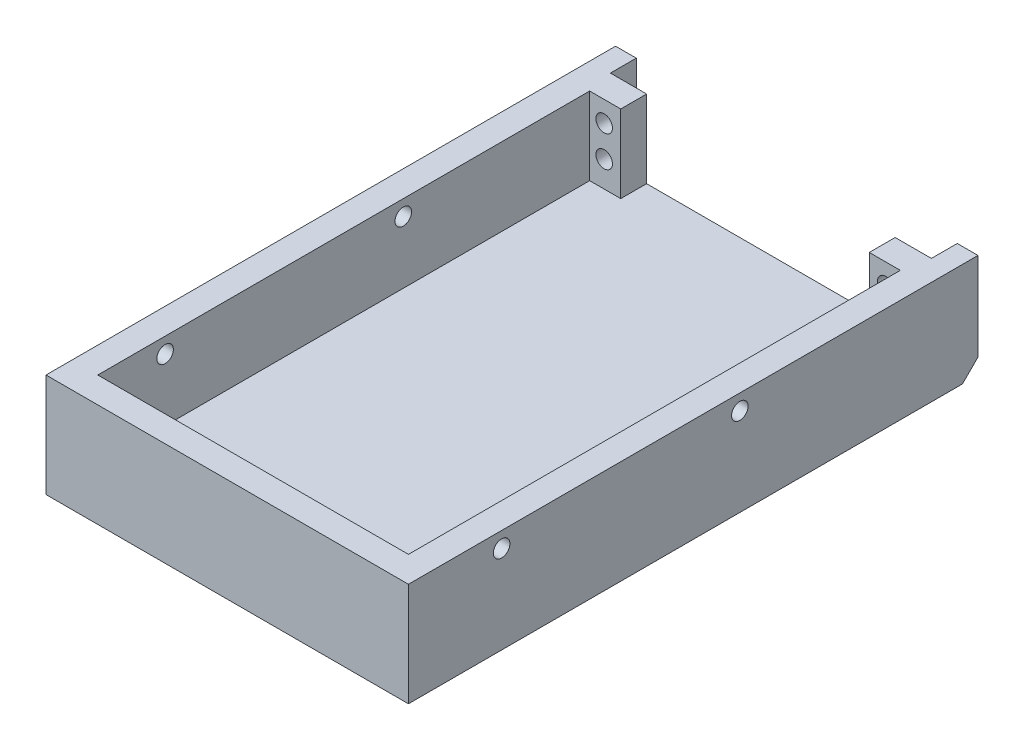
SolidWorks part; units mm, degrees
ref_plane "Alzado" through (0, 0, 0) normal (0, 0, 1) x (1, 0, 0)
ref_plane "Planta" through (0, 0, 0) normal (0, 1, 0) x (1, 0, 0)
ref_plane "Vista lateral" through (0, 0, 0) normal (1, 0, 0) x (0, 0, -1)
sketch "Croquis1" plane through (0, 0, 0) normal (0, 1, 0) x (1, 0, 0)
  line L1 (-35, -52.5) -> (35, -52.5)
  line L2 (-35, -52.5) -> (-35, 52.5)
  line L3 (-35, 52.5) -> (35, 52.5)
  line L4 (35, -52.5) -> (35, 52.5)
  line L5 (-35, -52.5) -> (35, 52.5) construction
  line L6 (-35, 52.5) -> (35, -52.5) construction
  point P0 (0, 0)
  dimension "D1" = 105
  dimension "D2" = 70
extrude "Saliente-Extruir1" add sketch "Croquis1" along normal blind 20
shell "Vaciado1" thickness 5 removed face at (0, 20, 0)
sketch "Croquis3" plane through (-35, 0, 0) normal (-1, 0, 0) x (0, 0, 1)
  line L0 (34.5, 17) -> (-11.5, 17) construction
  line L1 (52.5, 20) -> (52.5, 0) construction
  line L2 (-52.5, 20) -> (52.5, 20) construction
  circle A0 centre (34.5, 17) radius 1.6
  circle A1 centre (-11.5, 17) radius 1.6
  dimension "D1" = 3.2
  dimension "D2" = 3.2
  dimension "D3" = 46
  dimension "D4" = 18
  dimension "D5" = 3
extrude "Cortar-Extruir1" cut sketch "Croquis3" against normal blind 70
sketch "Croquis4" plane through (0, 0, -52.5) normal (0, 0, -1) x (-1, 0, 0)
  line L0 (-35, 20) -> (35, 20) construction
  line L1 (-30, 20) -> (30, 20)
  line L2 (-30, 20) -> (-30, 5)
  line L3 (-30, 5) -> (30, 5)
  line L4 (30, 20) -> (30, 5)
  line L5 (-35, 0) -> (35, 0) construction
  line L6 (35, 20) -> (35, 0) construction
  line L7 (-35, 20) -> (-35, 0) construction
  dimension "D1" = 5
  dimension "D2" = 5
  dimension "D3" = 5
extrude "Cortar-Extruir2" cut sketch "Croquis4" against normal blind 5
sketch "Croquis5" plane through (-30, 0, 0) normal (1, 0, 0) x (0, 0, -1)
  line L0 (-52.5, 20) -> (52.5, 20) construction
  line L1 (47.5, 20) -> (52.5, 20)
  line L2 (47.5, 20) -> (47.5, 5)
  line L3 (47.5, 5) -> (52.5, 5)
  line L4 (52.5, 20) -> (52.5, 5)
  dimension "D1" = 5
extrude "Saliente-Extruir2" add sketch "Croquis5" along normal blind 6
mirror "Simetría1" about plane through (0, 0, 0) normal (1, 0, 0) of "Saliente-Extruir2"
sketch "Croquis6" plane through (0, 0, -52.5) normal (0, 0, -1) x (-1, 0, 0)
  line L0 (-27.2, 16) -> (-27.2, 10) construction
  line L1 (-35, 20) -> (-24, 20) construction
  line L2 (-24, 5) -> (-24, 20) construction
  line L3 (-35, 20) -> (-35, 0) construction
  line L4 (-35, 0) -> (35, 0) construction
  circle A0 centre (-27.2, 16) radius 1.6
  circle A1 centre (-27.2, 10) radius 1.6
  dimension "D1" = 3.2
  dimension "D2" = 3.2
  dimension "D3" = 4
  dimension "D4" = 6
  dimension "D5" = 3.2
extrude "Cortar-Extruir3" cut sketch "Croquis6" against normal up to next
mirror "Simetría2" about plane through (0, 0, 0) normal (1, 0, 0) of "Cortar-Extruir3"
sketch "Croquis7" plane through (0, 0, 0) normal (0, 1, 0) x (1, 0, 0)
  line L0 (35, 57.5) -> (31, 57.5) construction
  line L1 (35, 57.5) -> (31, 57.5)
  line L2 (35, 57.5) -> (35, 52.5)
  line L3 (35, 52.5) -> (31, 52.5)
  line L4 (31, 57.5) -> (31, 52.5)
  point P6 (31.5357, 57.5)
  point P7 (31.7237, 57.5)
  point P8 (32.9266, 57.5)
  point P9 (31.0245, 57.5)
  point P10 (0, 0)
  point P11 (0, 0)
  point P12 (31, 52.2852)
  point P13 (31, 52.2852)
  point P14 (35, 52.5)
  point P16 (0, 0)
  point P17 (35, 57.5)
  point P18 (35, 57.624)
  point P19 (35, 57.4485)
  point P20 (35, 57.492)
  point P21 (31, 57.4093)
  point P22 (35, 56.2398)
  point P23 (35, 59.0477)
  point P24 (31, 57.5)
  dimension "D1" = 4
extrude "Saliente-Extruir3" add sketch "Croquis7" along normal up to surface (20 mm away) up to face at (0, 20, -16.6667)
chamfer "Chaflán1" distance 3 angle 45 1 edges at (33, 0, -57.5)
mirror "Simetría3" about plane through (0, 0, 0) normal (1, 0, 0) of "Chaflán1", "Saliente-Extruir3"
